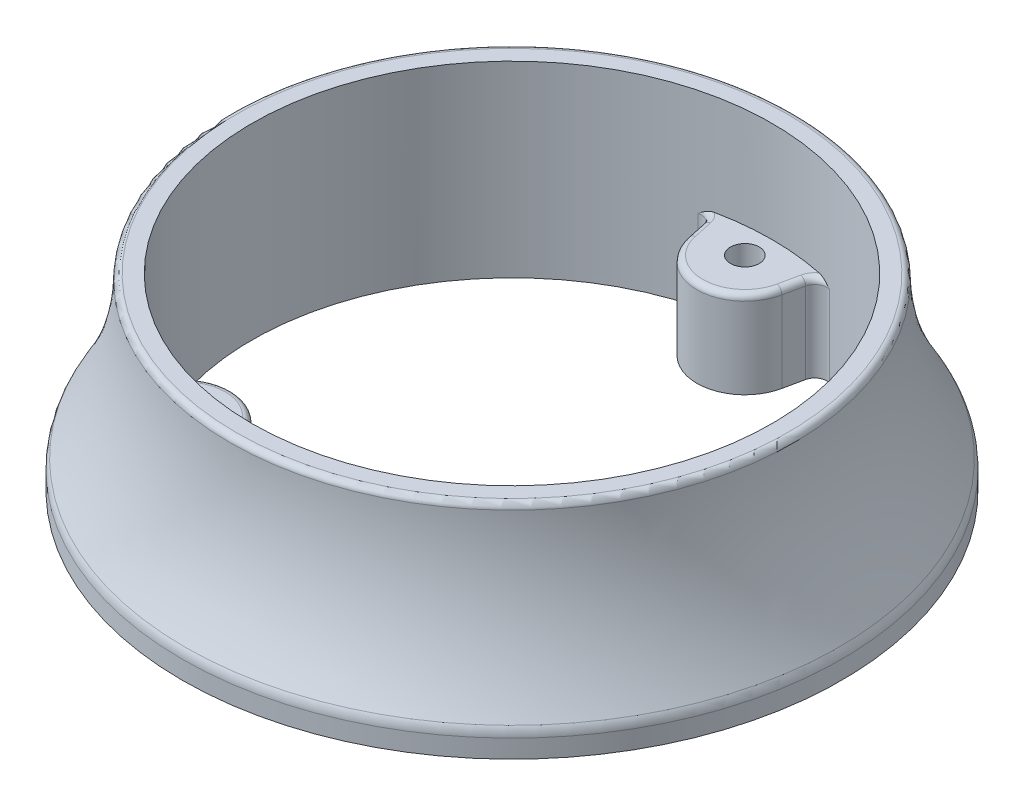
SolidWorks part; units mm, degrees
ref_plane "Ebene vorne" through (0, 0, 0) normal (0, 0, 1) x (1, 0, 0)
ref_plane "Ebene oben" through (0, 0, 0) normal (0, 1, 0) x (1, 0, 0)
ref_plane "Ebene rechts" through (0, 0, 0) normal (1, 0, 0) x (0, 0, -1)
sketch "Skizze1" plane through (0, 0, 0) normal (0, 1, 0) x (1, 0, 0)
  circle A0 centre (0, 0) radius 21.7
  circle A1 centre (0, 0) radius 23.5
extrude "Aufsatz-Linear austragen1" add sketch "Skizze1" along normal blind 8.4
sketch "Skizze2" plane through (0, 0, 0) normal (0, 1, 0) x (1, 0, 0)
  line L0 (-3.9145, 18.6075) -> (-4.2564, 20.233)
  line L1 (3.9145, 18.6075) -> (4.2564, 20.233)
  line L2 (-14.4417, -12.6076) -> (-15.5756, -13.5975)
  line L3 (-8.1947, -17.3309) -> (-8.8381, -18.6916)
  line L4 (8.1937, -17.3311) -> (8.8372, -18.6921)
  line L5 (14.4422, -12.6067) -> (15.5763, -13.5967)
  arc A0 (-5.4879, 20.9946) -> (-17.0175, -13.4646) centre (0, 0) ccw
  circle A1 centre (0, 0) radius 23.5
  circle A2 centre (0, 19.431) radius 1.2
  circle A3 centre (-11.811, -15.621) radius 1.2
  circle A4 centre (11.811, -15.621) radius 1.2
  arc A5 (-3.9145, 18.6075) -> (3.9145, 18.6075) centre (0, 19.431) ccw
  arc A6 (-8.1947, -17.3309) -> (-14.4417, -12.6076) centre (-11.811, -15.621) ccw
  arc A7 (14.4422, -12.6067) -> (8.1937, -17.3311) centre (11.811, -15.621) ccw
  arc A8 (-8.3174, -20.0427) -> (8.3164, -20.0432) centre (0, 0) ccw
  arc A9 (17.0181, -13.4638) -> (5.4879, 20.9946) centre (0, 0) ccw
  arc A10 (-4.2564, 20.233) -> (-5.4879, 20.9946) centre (-5.235, 20.0271) ccw
  arc A11 (4.2564, 20.233) -> (5.4879, 20.9946) centre (5.235, 20.0271) cw
  arc A12 (15.5763, -13.5967) -> (17.0181, -13.4638) centre (16.2339, -12.8433) ccw
  arc A13 (8.8372, -18.6921) -> (8.3164, -20.0432) centre (7.9331, -19.1195) cw
  arc A14 (-8.8381, -18.6916) -> (-8.3174, -20.0427) centre (-7.9341, -19.1191) ccw
  arc A15 (-15.5756, -13.5975) -> (-17.0175, -13.4646) centre (-16.2332, -12.8441) cw
  point P30 (16.3478, -14.2702)
  point P33 (9.2749, -19.618)
  point P36 (-9.2759, -19.6175)
  dimension "D1" = 1
extrude "Aufsatz-Linear austragen2" add sketch "Skizze2" against normal up to surface (7.2595 mm away)
sketch "Skizze3" plane through (0, 0, 0) normal (0, 0, 1) x (1, 0, 0)
  line L0 (0, 8.4) -> (0, -7.2595)
  line L1 (23.5, 8.4) -> (-23.5, 8.4) construction
  line L2 (-23.5, -7.2595) -> (23.5, -7.2595) construction
  line L3 (23.5, 8.4) -> (23.5, -7.2595)
  line L4 (23.5, -7.2595) -> (27.5, -7.2595)
  line L5 (27.5, -7.2595) -> (27.5, -5.7369)
  arc A0 (27.5, -5.7369) -> (27.2854, -4.9637) centre (26, -5.7369) ccw
  spline S0 degree 3 poles (23.5, 8.4) (23.5, 6.043) (24.1309, 1.4587) (26.0236, -2.8661) (27.2854, -4.9637) knots 0 0 0 0 0.4864 0.972801 0.972801 0.972801 0.972801
  dimension "D1" = 1.5
revolve "Rotation1" add sketch "Skizze3" angle 360 about L0 region at (24.9337, -3.269, 0)
fillet "Verrundung1" radius 0.5 1 edges at (0, 8.4, 23.5)
fillet "Verrundung2" radius 0.5 15 edges at (-16.325, 0, 13.8399) (-15.0086, 0, 13.1025) (-8.8672, 0, 19.4787) (-8.5164, 0, 18.0113) (8.8662, 0, 19.4792) (8.5155, 0, 18.0116) (16.3257, 0, 13.8391) (15.0092, 0, 13.1017) (4.709, 0, -20.8776) (4.0855, 0, -19.4202) (-4.709, 0, -20.8776) (-4.0855, 0, -19.4202) (-9.3985, 0, 12.4302) (9.3979, 0, 12.4295) (0, 0, -15.4308)
